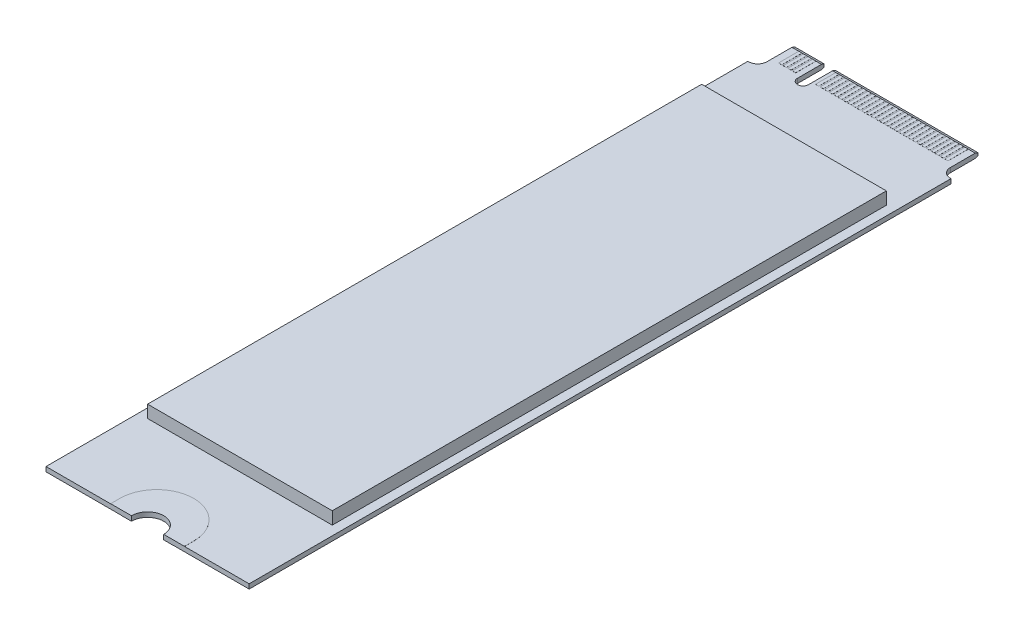
SolidWorks part; units mm, degrees
ref_plane "Front" through (0, 0, 0) normal (0, 0, 1) x (1, 0, 0)
ref_plane "Top" through (0, 0, 0) normal (0, 1, 0) x (1, 0, 0)
ref_plane "Right" through (0, 0, 0) normal (1, 0, 0) x (0, 0, -1)
sketch "Sketch1" plane through (0, 0, 0) normal (0, 1, 0) x (1, 0, 0)
  line L0 (0, 0) -> (0, 65.3465) construction
  line L1 (1.75, -40) -> (11, -40)
  line L2 (0, 40) -> (-5.525, 40)
  line L3 (-11, 36) -> (-11, -40)
  line L4 (-11, -40) -> (-1.75, -40)
  line L5 (11, 36) -> (11, -40)
  line L6 (-11, 36) -> (-10.925, 36)
  line L7 (-9.925, 40) -> (-9.925, 37)
  line L8 (9.925, 40) -> (9.925, 37)
  line L9 (10.925, 36) -> (11, 36)
  line L10 (-5.525, 37.1) -> (-5.525, 40)
  line L11 (6.225, 40) -> (9.925, 40)
  line L12 (-6.725, 37.1) -> (-6.725, 40)
  line L13 (-9.925, 40) -> (-6.725, 40)
  line L14 (0, 40) -> (5.025, 40)
  line L16 (5.025, 37.1) -> (5.025, 40)
  line L17 (6.225, 37.1) -> (6.225, 40)
  arc A0 (1.75, -40) -> (-1.75, -40) centre (0, -40) ccw
  arc A1 (9.925, 37) -> (10.925, 36) centre (10.925, 37) ccw
  arc A2 (-9.925, 37) -> (-10.925, 36) centre (-10.925, 37) cw
  arc A3 (-6.725, 37.1) -> (-5.525, 37.1) centre (-6.125, 37.1) ccw
  arc A4 (5.025, 37.1) -> (6.225, 37.1) centre (5.625, 37.1) ccw
  point P3 (-11, 40)
  point P6 (11, 40)
  point P18 (9.925, 36)
  dimension "D2" = 1
  dimension "D1" = 11
  dimension "D3" = 40
  dimension "D4" = 22
extrude "Boss-Extrude1" add sketch "Sketch1" against normal blind 0.5
sketch "Sketch5" plane through (9.925, 0, 0) normal (1, 0, 0) x (0, 0, -1)
  line L0 (40, 0) -> (39.7, 0)
  line L1 (37, 0) -> (40, 0) construction
  line L2 (40, 0) -> (40, -0.1092)
  line L3 (40, -0.1092) -> (39.7, 0)
  line L4 (40, -0.25) -> (38.9715, -0.25) construction
  line L5 (40, -0.5) -> (40, 0) construction
  line L6 (40, -0.3908) -> (39.7, -0.5)
  line L7 (40, -0.5) -> (40, -0.3908)
  line L8 (40, -0.5) -> (39.7, -0.5)
  dimension "D1" = 20
extrude "Cut-Extrude2" cut sketch "Sketch5" against normal through all
sketch "Sketch7" plane through (0, 0, 0) normal (0, 1, 0) x (1, 0, 0)
  line L1 (-10, 30) -> (10, 30)
  line L2 (-10, 30) -> (-10, -30)
  line L3 (-10, -30) -> (10, -30)
  line L4 (10, 30) -> (10, -30)
  arc A0 (1.75, -40) -> (-1.75, -40) centre (0, -40) ccw construction
  point P7 (0, -38.25)
  dimension "D1" = 60
  dimension "D2" = 20
  dimension "D3" = 10
  dimension "D4" = 30
extrude "Boss-Extrude3" add sketch "Sketch7" along normal blind 1.35
sketch "Sketch8" [suppressed] plane through (0, -0.5, 0) normal (0, -1, 0) x (1, 0, 0)
  line L1 (-10, 30) -> (10, 30)
  line L2 (-10, 30) -> (-10, -30)
  line L3 (-10, -30) -> (10, -30)
  line L4 (10, 30) -> (10, -30)
extrude "Boss-Extrude4" [suppressed] add sketch "Sketch8" along normal blind 1.35
sketch "Sketch12" plane through (0, -0.5, 0) normal (0, -1, 0) x (1, 0, 0)
  line L0 (-2.75, 40) -> (-1.75, 40)
  line L1 (1.75, 40) -> (2.75, 40)
  arc A1 (-1.75, 40) -> (1.75, 40) centre (0, 40) ccw construction
  arc A4 (-1.75, 40) -> (1.75, 40) centre (0, 40) ccw
  arc A5 (-2.75, 40) -> (2.75, 40) centre (0, 40) ccw
  dimension "D2" = 5.5
extrude "Boss-Extrude6" add sketch "Sketch12" along normal blind 0.01
ref_plane "Plane2" through (0, -0.25, 0) normal (0, 1, 0) x (1, 0, 0)
sketch "Sketch15" plane through (0, 0, 0) normal (0, 1, 0) x (1, 0, 0)
  line L0 (-4, -40) -> (-4, -39)
  line L1 (4, -40) -> (4, -39)
  line L2 (-4, -40) -> (-1.75, -40)
  line L3 (1.75, -40) -> (4, -40)
  arc A0 (1.75, -40) -> (-1.75, -40) centre (0, -40) ccw construction
  arc A1 (1.75, -40) -> (-1.75, -40) centre (0, -40) ccw
  arc A2 (4, -39) -> (-4, -39) centre (0, -39) ccw
extrude "Boss-Extrude9" add sketch "Sketch15" along normal blind 0.01
sketch "Sketch16" plane through (6.225, 0, 0) normal (-1, 0, 0) x (0, 0, 1)
  line L0 (-39.7, -0.5) -> (-40, -0.3908) construction
  line L1 (-40, -0.3908) -> (-40, -0.1092) construction
  line L2 (-40, -0.1092) -> (-39.7, 0) construction
  line L3 (-39.7, 0) -> (-37.1, 0) construction
  line L4 (-37.1, -0.5) -> (-37.1, 0) construction
  line L5 (-39.7, -0.5) -> (-37.1, -0.5) construction
  line L6 (-39.7, -0.5) -> (-40, -0.3908)
  line L7 (-40, -0.3908) -> (-40, -0.1092)
  line L8 (-40, -0.1092) -> (-39.7, 0)
  line L9 (-39.7, 0) -> (-37.1, 0)
  line L10 (-37.1, -0.5) -> (-37.1, 0)
  line L11 (-39.7, -0.5) -> (-37.1, -0.5)
extrude "Boss-Extrude10" add sketch "Sketch16" along normal up to next
sketch "Sketch17" plane through (0, -0.5, 0) normal (0, -1, 0) x (1, 0, 0)
  line L0 (5.025, -37.1) -> (6.225, -37.1) construction
  line L1 (5.025, -37.1) -> (6.225, -37.1)
  arc A0 (6.225, -37.1) -> (5.025, -37.1) centre (5.625, -37.1) ccw construction
  arc A1 (6.225, -37.1) -> (5.025, -37.1) centre (5.625, -37.1) ccw
extrude "Boss-Extrude11" add sketch "Sketch17" against normal up to surface (0.5 mm away) up to face at (-1.3611, 0, -11.9992)
sketch "Sketch18" plane through (0, -0.5, 0) normal (0, -1, 0) x (1, 0, 0)
  line L0 (0, 0) -> (0, -40) construction
  line L1 (-5.525, -40) -> (9.925, -40) construction
  line L3 (-9.4173, -38) -> (-9.0701, -38)
  line L4 (-8.9173, -38) -> (-8.5701, -38)
  line L5 (-8.9173, -38) -> (-8.9173, -39.7)
  line L6 (-9.925, -39.7) -> (-6.725, -39.7) construction
  line L7 (-9.4173, -38) -> (-9.4173, -39.7)
  line L8 (-9.0701, -38) -> (-9.0701, -39.7)
  line L9 (-9.0701, -39.7) -> (-9.4173, -39.7)
  line L10 (-8.5701, -38) -> (-8.5701, -39.7)
  line L11 (-8.5701, -39.7) -> (-8.9173, -39.7)
  line L12 (-8.4173, -38) -> (-8.0701, -38)
  line L13 (-8.4173, -38) -> (-8.4173, -39.7)
  line L14 (-8.0701, -38) -> (-8.0701, -39.7)
  line L15 (-8.0701, -39.7) -> (-8.4173, -39.7)
  line L16 (-7.9173, -38) -> (-7.5701, -38)
  line L17 (-7.9173, -38) -> (-7.9173, -39.7)
  line L18 (-7.5701, -38) -> (-7.5701, -39.7)
  line L19 (-7.5701, -39.7) -> (-7.9173, -39.7)
  line L20 (-7.4173, -38) -> (-7.0701, -38)
  line L21 (-7.4173, -38) -> (-7.4173, -39.7)
  line L22 (-7.0701, -38) -> (-7.0701, -39.7)
  line L23 (-7.0701, -39.7) -> (-7.4173, -39.7)
extrude "Boss-Extrude12" add sketch "Sketch18" along normal blind 0.01
sketch "Sketch19" plane through (0, -0.5, 0) normal (0, -1, 0) x (1, 0, 0)
  line L0 (0, 0) -> (0, -39.7) construction
  line L1 (-5.525, -39.7) -> (9.925, -39.7) construction
  line L3 (9.075, -38) -> (9.425, -38)
  line L4 (9.075, -39.7) -> (9.425, -39.7)
  line L5 (8.575, -38) -> (8.925, -38)
  line L6 (9.075, -38) -> (9.075, -39.7)
  line L7 (9.425, -38) -> (9.425, -39.7)
  line L8 (8.575, -39.7) -> (8.925, -39.7)
  line L9 (8.575, -38) -> (8.575, -39.7)
  line L10 (8.925, -38) -> (8.925, -39.7)
  line L11 (8.075, -38) -> (8.425, -38)
  line L12 (8.075, -39.7) -> (8.425, -39.7)
  line L13 (8.075, -38) -> (8.075, -39.7)
  line L14 (8.425, -38) -> (8.425, -39.7)
  line L15 (7.575, -38) -> (7.925, -38)
  line L16 (7.575, -39.7) -> (7.925, -39.7)
  line L17 (7.575, -38) -> (7.575, -39.7)
  line L18 (7.925, -38) -> (7.925, -39.7)
  line L19 (7.075, -38) -> (7.425, -38)
  line L20 (7.075, -39.7) -> (7.425, -39.7)
  line L21 (7.075, -38) -> (7.075, -39.7)
  line L22 (7.425, -38) -> (7.425, -39.7)
  line L23 (6.575, -38) -> (6.925, -38)
  line L24 (6.575, -39.7) -> (6.925, -39.7)
  line L25 (6.575, -38) -> (6.575, -39.7)
  line L26 (6.925, -38) -> (6.925, -39.7)
  line L27 (6.075, -38) -> (6.425, -38)
  line L28 (6.075, -39.7) -> (6.425, -39.7)
  line L29 (6.075, -38) -> (6.075, -39.7)
  line L30 (6.425, -38) -> (6.425, -39.7)
  line L31 (5.575, -38) -> (5.925, -38)
  line L32 (5.575, -39.7) -> (5.925, -39.7)
  line L33 (5.575, -38) -> (5.575, -39.7)
  line L34 (5.925, -38) -> (5.925, -39.7)
  line L35 (5.075, -38) -> (5.425, -38)
  line L36 (5.075, -39.7) -> (5.425, -39.7)
  line L37 (5.075, -38) -> (5.075, -39.7)
  line L38 (5.425, -38) -> (5.425, -39.7)
  line L39 (4.575, -38) -> (4.925, -38)
  line L40 (4.575, -39.7) -> (4.925, -39.7)
  line L41 (4.575, -38) -> (4.575, -39.7)
  line L42 (4.925, -38) -> (4.925, -39.7)
  line L43 (4.075, -38) -> (4.425, -38)
  line L44 (4.075, -39.7) -> (4.425, -39.7)
  line L45 (4.075, -38) -> (4.075, -39.7)
  line L46 (4.425, -38) -> (4.425, -39.7)
  line L47 (3.575, -38) -> (3.925, -38)
  line L48 (3.575, -39.7) -> (3.925, -39.7)
  line L49 (3.575, -38) -> (3.575, -39.7)
  line L50 (3.925, -38) -> (3.925, -39.7)
  line L51 (3.075, -38) -> (3.425, -38)
  line L52 (3.075, -39.7) -> (3.425, -39.7)
  line L53 (3.075, -38) -> (3.075, -39.7)
  line L54 (3.425, -38) -> (3.425, -39.7)
  line L55 (2.575, -38) -> (2.925, -38)
  line L56 (2.575, -39.7) -> (2.925, -39.7)
  line L57 (2.575, -38) -> (2.575, -39.7)
  line L58 (2.925, -38) -> (2.925, -39.7)
  line L59 (2.075, -38) -> (2.425, -38)
  line L60 (2.075, -39.7) -> (2.425, -39.7)
  line L61 (2.075, -38) -> (2.075, -39.7)
  line L62 (2.425, -38) -> (2.425, -39.7)
  line L63 (1.575, -38) -> (1.925, -38)
  line L64 (1.575, -39.7) -> (1.925, -39.7)
  line L65 (1.575, -38) -> (1.575, -39.7)
  line L66 (1.925, -38) -> (1.925, -39.7)
  line L67 (1.075, -38) -> (1.425, -38)
  line L68 (1.075, -39.7) -> (1.425, -39.7)
  line L69 (1.075, -38) -> (1.075, -39.7)
  line L70 (1.425, -38) -> (1.425, -39.7)
  line L71 (0.575, -38) -> (0.925, -38)
  line L72 (0.575, -39.7) -> (0.925, -39.7)
  line L73 (0.575, -38) -> (0.575, -39.7)
  line L74 (0.925, -38) -> (0.925, -39.7)
  line L75 (0.075, -38) -> (0.425, -38)
  line L76 (0.075, -39.7) -> (0.425, -39.7)
  line L77 (0.075, -38) -> (0.075, -39.7)
  line L78 (0.425, -38) -> (0.425, -39.7)
  line L79 (-0.425, -38) -> (-0.075, -38)
  line L80 (-0.425, -39.7) -> (-0.075, -39.7)
  line L81 (-0.425, -38) -> (-0.425, -39.7)
  line L82 (-0.075, -38) -> (-0.075, -39.7)
  line L83 (-0.925, -38) -> (-0.575, -38)
  line L84 (-0.925, -39.7) -> (-0.575, -39.7)
  line L85 (-0.925, -38) -> (-0.925, -39.7)
  line L86 (-0.575, -38) -> (-0.575, -39.7)
  line L87 (-1.425, -38) -> (-1.075, -38)
  line L88 (-1.425, -39.7) -> (-1.075, -39.7)
  line L89 (-1.425, -38) -> (-1.425, -39.7)
  line L90 (-1.075, -38) -> (-1.075, -39.7)
  line L91 (-1.925, -38) -> (-1.575, -38)
  line L92 (-1.925, -39.7) -> (-1.575, -39.7)
  line L93 (-1.925, -38) -> (-1.925, -39.7)
  line L94 (-1.575, -38) -> (-1.575, -39.7)
  line L95 (-2.425, -38) -> (-2.075, -38)
  line L96 (-2.425, -39.7) -> (-2.075, -39.7)
  line L97 (-2.425, -38) -> (-2.425, -39.7)
  line L98 (-2.075, -38) -> (-2.075, -39.7)
  line L99 (-2.925, -38) -> (-2.575, -38)
  line L100 (-2.925, -39.7) -> (-2.575, -39.7)
  line L101 (-2.925, -38) -> (-2.925, -39.7)
  line L102 (-2.575, -38) -> (-2.575, -39.7)
  line L103 (-3.425, -38) -> (-3.075, -38)
  line L104 (-3.425, -39.7) -> (-3.075, -39.7)
  line L105 (-3.425, -38) -> (-3.425, -39.7)
  line L106 (-3.075, -38) -> (-3.075, -39.7)
  line L107 (-3.925, -38) -> (-3.575, -38)
  line L108 (-3.925, -39.7) -> (-3.575, -39.7)
  line L109 (-3.925, -38) -> (-3.925, -39.7)
  line L110 (-3.575, -38) -> (-3.575, -39.7)
  line L111 (-4.425, -38) -> (-4.075, -38)
  line L112 (-4.425, -39.7) -> (-4.075, -39.7)
  line L113 (-4.425, -38) -> (-4.425, -39.7)
  line L114 (-4.075, -38) -> (-4.075, -39.7)
  line L115 (-4.925, -38) -> (-4.575, -38)
  line L116 (-4.925, -39.7) -> (-4.575, -39.7)
  line L117 (-4.925, -38) -> (-4.925, -39.7)
  line L118 (-4.575, -38) -> (-4.575, -39.7)
extrude "Boss-Extrude13" add sketch "Sketch19" along normal blind 0.01
sketch "Sketch21" plane through (0, 0, 0) normal (0, 1, 0) x (1, 0, 0)
  line L0 (8.3278, 39.7) -> (8.6778, 39.7)
  line L1 (9.003, 35.183) -> (9.0027, 38.073) construction
  line L2 (8.3278, 37.5) -> (8.3278, 39.7)
  line L3 (8.6778, 39.7) -> (8.6778, 37.5)
  line L4 (8.928, 35.183) -> (9.078, 35.183) construction
  line L5 (8.9277, 38.073) -> (9.0777, 38.073) construction
  line L6 (8.5027, 38.0729) -> (8.503, 35.1829) construction
  line L7 (8.4277, 38.0729) -> (8.5777, 38.0729) construction
  line L8 (8.428, 35.1829) -> (8.578, 35.1829) construction
  line L12 (8.8278, 39.7) -> (9.1778, 39.7)
  line L13 (8.8278, 37.5) -> (8.8278, 39.7)
  line L14 (9.1778, 39.7) -> (9.1778, 37.5)
  line L15 (8.8278, 37.5) -> (9.1778, 37.5)
  line L16 (8.3278, 37.5) -> (8.6778, 37.5)
  line L17 (7.8278, 39.7) -> (8.1778, 39.7)
  line L18 (7.8278, 37.5) -> (7.8278, 39.7)
  line L19 (8.1778, 39.7) -> (8.1778, 37.5)
  line L20 (7.8278, 37.5) -> (8.1778, 37.5)
  line L21 (7.3278, 39.7) -> (7.6778, 39.7)
  line L22 (7.3278, 37.5) -> (7.3278, 39.7)
  line L23 (7.6778, 39.7) -> (7.6778, 37.5)
  line L24 (7.3278, 37.5) -> (7.6778, 37.5)
  line L25 (6.8278, 39.7) -> (7.1778, 39.7)
  line L26 (6.8278, 37.5) -> (6.8278, 39.7)
  line L27 (7.1778, 39.7) -> (7.1778, 37.5)
  line L28 (6.8278, 37.5) -> (7.1778, 37.5)
  line L29 (6.3278, 39.7) -> (6.6778, 39.7)
  line L30 (6.3278, 37.5) -> (6.3278, 39.7)
  line L31 (6.6778, 39.7) -> (6.6778, 37.5)
  line L32 (6.3278, 37.5) -> (6.6778, 37.5)
  line L33 (5.8278, 39.7) -> (6.1778, 39.7)
  line L34 (5.8278, 37.5) -> (5.8278, 39.7)
  line L35 (6.1778, 39.7) -> (6.1778, 37.5)
  line L36 (5.8278, 37.5) -> (6.1778, 37.5)
  line L37 (5.3278, 39.7) -> (5.6778, 39.7)
  line L38 (5.3278, 37.5) -> (5.3278, 39.7)
  line L39 (5.6778, 39.7) -> (5.6778, 37.5)
  line L40 (5.3278, 37.5) -> (5.6778, 37.5)
  line L41 (4.8278, 39.7) -> (5.1778, 39.7)
  line L42 (4.8278, 37.5) -> (4.8278, 39.7)
  line L43 (5.1778, 39.7) -> (5.1778, 37.5)
  line L44 (4.8278, 37.5) -> (5.1778, 37.5)
  line L45 (4.3278, 39.7) -> (4.6778, 39.7)
  line L46 (4.3278, 37.5) -> (4.3278, 39.7)
  line L47 (4.6778, 39.7) -> (4.6778, 37.5)
  line L48 (4.3278, 37.5) -> (4.6778, 37.5)
  line L49 (3.8278, 39.7) -> (4.1778, 39.7)
  line L50 (3.8278, 37.5) -> (3.8278, 39.7)
  line L51 (4.1778, 39.7) -> (4.1778, 37.5)
  line L52 (3.8278, 37.5) -> (4.1778, 37.5)
  line L53 (3.3278, 39.7) -> (3.6778, 39.7)
  line L54 (3.3278, 37.5) -> (3.3278, 39.7)
  line L55 (3.6778, 39.7) -> (3.6778, 37.5)
  line L56 (3.3278, 37.5) -> (3.6778, 37.5)
  line L57 (2.8278, 39.7) -> (3.1778, 39.7)
  line L58 (2.8278, 37.5) -> (2.8278, 39.7)
  line L59 (3.1778, 39.7) -> (3.1778, 37.5)
  line L60 (2.8278, 37.5) -> (3.1778, 37.5)
  line L61 (2.3278, 39.7) -> (2.6778, 39.7)
  line L62 (2.3278, 37.5) -> (2.3278, 39.7)
  line L63 (2.6778, 39.7) -> (2.6778, 37.5)
  line L64 (2.3278, 37.5) -> (2.6778, 37.5)
  line L65 (1.8278, 39.7) -> (2.1778, 39.7)
  line L66 (1.8278, 37.5) -> (1.8278, 39.7)
  line L67 (2.1778, 39.7) -> (2.1778, 37.5)
  line L68 (1.8278, 37.5) -> (2.1778, 37.5)
  line L69 (1.3278, 39.7) -> (1.6778, 39.7)
  line L70 (1.3278, 37.5) -> (1.3278, 39.7)
  line L71 (1.6778, 39.7) -> (1.6778, 37.5)
  line L72 (1.3278, 37.5) -> (1.6778, 37.5)
  line L73 (0.8278, 39.7) -> (1.1778, 39.7)
  line L74 (0.8278, 37.5) -> (0.8278, 39.7)
  line L75 (1.1778, 39.7) -> (1.1778, 37.5)
  line L76 (0.8278, 37.5) -> (1.1778, 37.5)
  line L77 (0.3278, 39.7) -> (0.6778, 39.7)
  line L78 (0.3278, 37.5) -> (0.3278, 39.7)
  line L79 (0.6778, 39.7) -> (0.6778, 37.5)
  line L80 (0.3278, 37.5) -> (0.6778, 37.5)
  line L81 (-0.1722, 39.7) -> (0.1778, 39.7)
  line L82 (-0.1722, 37.5) -> (-0.1722, 39.7)
  line L83 (0.1778, 39.7) -> (0.1778, 37.5)
  line L84 (-0.1722, 37.5) -> (0.1778, 37.5)
  line L85 (-0.6722, 39.7) -> (-0.3222, 39.7)
  line L86 (-0.6722, 37.5) -> (-0.6722, 39.7)
  line L87 (-0.3222, 39.7) -> (-0.3222, 37.5)
  line L88 (-0.6722, 37.5) -> (-0.3222, 37.5)
  line L89 (-1.1722, 39.7) -> (-0.8222, 39.7)
  line L90 (-1.1722, 37.5) -> (-1.1722, 39.7)
  line L91 (-0.8222, 39.7) -> (-0.8222, 37.5)
  line L92 (-1.1722, 37.5) -> (-0.8222, 37.5)
  line L93 (-1.6722, 39.7) -> (-1.3222, 39.7)
  line L94 (-1.6722, 37.5) -> (-1.6722, 39.7)
  line L95 (-1.3222, 39.7) -> (-1.3222, 37.5)
  line L96 (-1.6722, 37.5) -> (-1.3222, 37.5)
  line L97 (-2.1722, 39.7) -> (-1.8222, 39.7)
  line L98 (-2.1722, 37.5) -> (-2.1722, 39.7)
  line L99 (-1.8222, 39.7) -> (-1.8222, 37.5)
  line L100 (-2.1722, 37.5) -> (-1.8222, 37.5)
  line L101 (-2.6722, 39.7) -> (-2.3222, 39.7)
  line L102 (-2.6722, 37.5) -> (-2.6722, 39.7)
  line L103 (-2.3222, 39.7) -> (-2.3222, 37.5)
  line L104 (-2.6722, 37.5) -> (-2.3222, 37.5)
  line L105 (-3.1722, 39.7) -> (-2.8222, 39.7)
  line L106 (-3.1722, 37.5) -> (-3.1722, 39.7)
  line L107 (-2.8222, 39.7) -> (-2.8222, 37.5)
  line L108 (-3.1722, 37.5) -> (-2.8222, 37.5)
  line L109 (-3.6722, 39.7) -> (-3.3222, 39.7)
  line L110 (-3.6722, 37.5) -> (-3.6722, 39.7)
  line L111 (-3.3222, 39.7) -> (-3.3222, 37.5)
  line L112 (-3.6722, 37.5) -> (-3.3222, 37.5)
  line L113 (-4.1722, 39.7) -> (-3.8222, 39.7)
  line L114 (-4.1722, 37.5) -> (-4.1722, 39.7)
  line L115 (-3.8222, 39.7) -> (-3.8222, 37.5)
  line L116 (-4.1722, 37.5) -> (-3.8222, 37.5)
  line L117 (-4.6722, 39.7) -> (-4.3222, 39.7)
  line L118 (-4.6722, 37.5) -> (-4.6722, 39.7)
  line L119 (-4.3222, 39.7) -> (-4.3222, 37.5)
  line L120 (-4.6722, 37.5) -> (-4.3222, 37.5)
  line L121 (-5.1722, 39.7) -> (-4.8222, 39.7)
  line L122 (-5.1722, 37.5) -> (-5.1722, 39.7)
  line L123 (-4.8222, 39.7) -> (-4.8222, 37.5)
  line L124 (-5.1722, 37.5) -> (-4.8222, 37.5)
  line L125 (-5.6722, 39.7) -> (-5.3222, 39.7) [skipped]
  line L126 (-5.6722, 37.5) -> (-5.6722, 39.7) [skipped]
  line L127 (-5.3222, 39.7) -> (-5.3222, 37.5) [skipped]
  line L128 (-5.6722, 37.5) -> (-5.3222, 37.5) [skipped]
  line L129 (-6.1722, 39.7) -> (-5.8222, 39.7) [skipped]
  line L130 (-6.1722, 37.5) -> (-6.1722, 39.7) [skipped]
  line L131 (-5.8222, 39.7) -> (-5.8222, 37.5) [skipped]
  line L132 (-6.1722, 37.5) -> (-5.8222, 37.5) [skipped]
  line L133 (-6.6722, 39.7) -> (-6.3222, 39.7) [skipped]
  line L134 (-6.6722, 37.5) -> (-6.6722, 39.7) [skipped]
  line L135 (-6.3222, 39.7) -> (-6.3222, 37.5) [skipped]
  line L136 (-6.6722, 37.5) -> (-6.3222, 37.5) [skipped]
  line L141 (-7.6722, 39.7) -> (-7.3222, 39.7)
  line L142 (-7.6722, 37.5) -> (-7.6722, 39.7)
  line L143 (-7.3222, 39.7) -> (-7.3222, 37.5)
  line L144 (-7.6722, 37.5) -> (-7.3222, 37.5)
  line L145 (-8.1722, 39.7) -> (-7.8222, 39.7)
  line L146 (-8.1722, 37.5) -> (-8.1722, 39.7)
  line L147 (-7.8222, 39.7) -> (-7.8222, 37.5)
  line L148 (-8.1722, 37.5) -> (-7.8222, 37.5)
  line L149 (-8.6722, 39.7) -> (-8.3222, 39.7)
  line L150 (-8.6722, 37.5) -> (-8.6722, 39.7)
  line L151 (-8.3222, 39.7) -> (-8.3222, 37.5)
  line L152 (-8.6722, 37.5) -> (-8.3222, 37.5)
  line L153 (-9.1722, 39.7) -> (-8.8222, 39.7)
  line L154 (-9.1722, 37.5) -> (-9.1722, 39.7)
  line L155 (-8.8222, 39.7) -> (-8.8222, 37.5)
  line L156 (-9.1722, 37.5) -> (-8.8222, 37.5)
  line L161 (-7.1722, 37.5) -> (-6.8222, 37.5) [skipped]
  line L162 (-6.8222, 39.7) -> (-6.8222, 37.5) [skipped]
  line L163 (-7.1722, 37.5) -> (-7.1722, 39.7) [skipped]
  line L164 (-7.1722, 39.7) -> (-6.8222, 39.7) [skipped]
  line L165 (-9.6722, 37.5) -> (-9.6722, 39.7) [skipped]
  line L166 (-9.6722, 37.5) -> (-9.3222, 37.5) [skipped]
  line L167 (-9.3222, 39.7) -> (-9.3222, 37.5) [skipped]
  line L168 (-9.6722, 39.7) -> (-9.3222, 39.7) [skipped]
  dimension "D1" = 38
extrude "Boss-Extrude15" add sketch "Sketch21" along normal blind 0.01
